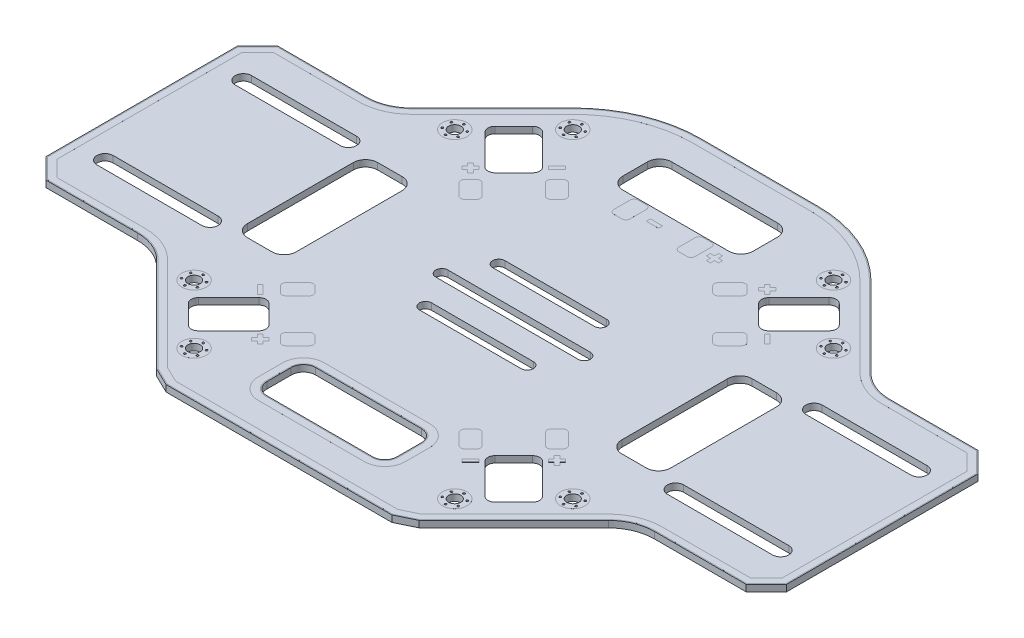
SolidWorks part; units mm, degrees
material "Baseplate Screw Material"
ref_plane "Front Plane" through (0, 0, 0) normal (0, 0, 1) x (1, 0, 0)
ref_plane "Top Plane" through (0, 0, 0) normal (0, 1, 0) x (1, 0, 0)
ref_plane "Right Plane" through (0, 0, 0) normal (1, 0, 0) x (0, 0, -1)
sketch "Sketch1" plane through (0, 0, 0) normal (0, 1, 0) x (1, 0, 0)
  line L0 (0, 60.3186) -> (0, -57.6814) construction
  line L1 (-27.75, -57.6814) -> (27.75, -57.6814)
  line L2 (-13, -47.6814) -> (13, -47.6814)
  line L3 (-16, -38.6814) -> (-16, -44.6814)
  line L4 (16, -38.6814) -> (16, -44.6814)
  line L5 (-16, -41.6814) -> (16, -41.6814) construction
  line L6 (-13, -35.6814) -> (13, -35.6814)
  line L7 (-27.75, -57.6814) -> (-32.25, -55.502)
  line L8 (27.75, -57.6814) -> (32.25, -55.502)
  line L9 (-32.25, -55.502) -> (32.25, -55.502) construction
  line L10 (32.25, -55.502) -> (55.502, -32.25)
  line L11 (-32.25, -55.502) -> (-55.502, -32.25)
  line L12 (-43.876, 43.876) -> (43.876, -43.876) construction
  line L13 (-43.876, -43.876) -> (43.876, 43.876) construction
  line L14 (37.6888, -42.285) -> (42.285, -37.6888)
  line L15 (27.7893, -34.8604) -> (35.2139, -42.285)
  line L16 (34.8604, -27.7893) -> (42.285, -35.2139)
  line L17 (31.5016, -38.5727) -> (38.5727, -31.5016) construction
  line L18 (27.7893, -32.3855) -> (32.3855, -27.7893)
  line L19 (-38.5727, -31.5016) -> (-31.5016, -38.5727) construction
  line L20 (-35.2139, -42.285) -> (-27.7893, -34.8604)
  line L21 (-42.285, -35.2139) -> (-34.8604, -27.7893)
  line L22 (-32.3855, -27.7893) -> (-27.7893, -32.3855)
  line L23 (-42.285, -37.6888) -> (-37.6888, -42.285)
  line L24 (-63.5, -28.9371) -> (63.5, -28.9371) construction
  line L25 (63.5, -28.9371) -> (86, -28.9371)
  line L26 (-63.5, -28.9371) -> (-86, -28.9371)
  line L27 (-91, -23.9371) -> (-91, 23.0629)
  line L28 (91, -23.9371) -> (91, 23.0629)
  line L29 (-86, -28.9371) -> (-86, 28.0629) construction
  line L30 (86, -28.9371) -> (86, 28.0629) construction
  line L31 (-91, -0.4371) -> (-86, -0.4371) construction
  line L32 (86, -0.4371) -> (91, -0.4371) construction
  line L33 (86, -28.9371) -> (91, -23.9371)
  line L34 (-91, -23.9371) -> (-86, -28.9371)
  line L35 (91, 23.0629) -> (86, 28.0629)
  line L36 (-91, 23.0629) -> (-86, 28.0629)
  line L37 (-56.4271, 31.3248) -> (-36.6281, 51.1238)
  line L38 (36.6281, 51.1238) -> (56.4271, 31.3248)
  line L39 (-35.2139, 42.285) -> (-27.7893, 34.8604)
  line L40 (-36.6281, 51.1238) -> (-27.7893, 42.285) construction
  line L41 (-27.7893, 42.285) -> (-31.5016, 38.5727) construction
  line L42 (-42.285, 35.2139) -> (-34.8604, 27.7893)
  line L43 (-31.5016, 38.5727) -> (-38.5727, 31.5016) construction
  line L44 (-42.285, 37.6888) -> (-37.6888, 42.285)
  line L45 (-32.3855, 27.7893) -> (-27.7893, 32.3855)
  line L46 (-86, 28.0629) -> (-64.3021, 28.0629)
  line L47 (86, 28.0629) -> (64.3021, 28.0629)
  line L48 (37.6888, 42.285) -> (42.285, 37.6888)
  line L49 (27.7893, 32.3855) -> (32.3855, 27.7893)
  line L50 (27.7893, 34.8604) -> (35.2139, 42.285)
  line L51 (34.8604, 27.7893) -> (42.285, 35.2139)
  line L52 (31.5016, 38.5727) -> (38.5727, 31.5016) construction
  line L53 (31.5016, 38.5727) -> (27.7893, 42.285) construction
  line L54 (27.7893, 42.285) -> (36.6281, 51.1238) construction
  line L55 (-14.43, 60.3186) -> (14.43, 60.3186)
  line L56 (-13, 51.8186) -> (13, 51.8186)
  line L57 (-13, 39.8186) -> (13, 39.8186)
  line L58 (16, 48.8186) -> (16, 42.8186)
  line L59 (-16, 48.8186) -> (-16, 42.8186)
  line L60 (-12.5, -10.6814) -> (12.5, -10.6814)
  line L61 (-12.5, -7.6814) -> (12.5, -7.6814)
  line L62 (-17.5, -1.6814) -> (17.5, -1.6814)
  line L63 (-17.5, 1.3186) -> (17.5, 1.3186)
  line L64 (-12.5, 7.3186) -> (12.5, 7.3186)
  line L65 (-12.5, 10.3186) -> (12.5, 10.3186)
  line L66 (-52, 12.5629) -> (-52, -13.4371)
  line L67 (-86, -0.4371) -> (-52, -0.4371) construction
  line L68 (-40, 12.5629) -> (-40, -13.4371)
  line L69 (52, 12.5629) -> (52, -13.4371)
  line L70 (-49, 15.5629) -> (-43, 15.5629)
  line L71 (-49, -16.4371) -> (-43, -16.4371)
  line L72 (86, -0.4371) -> (52, -0.4371) construction
  line L73 (40, 12.5629) -> (40, -13.4371)
  line L74 (43, 15.5629) -> (49, 15.5629)
  line L75 (43, -16.4371) -> (49, -16.4371)
  line L76 (-83, 18.5629) -> (-57.2, 18.5629)
  line L77 (-83, 14.5629) -> (-57.2, 14.5629)
  line L78 (-83, -15.4371) -> (-57.2, -15.4371)
  line L79 (-83, -19.4371) -> (-57.2, -19.4371)
  line L80 (57.2, -15.4371) -> (83, -15.4371)
  line L81 (57.2, -19.4371) -> (83, -19.4371)
  line L82 (57.2, 18.5629) -> (83, 18.5629)
  line L83 (57.2, 14.5629) -> (83, 14.5629)
  line L84 (-46.5276, 32.0319) -> (-32.0319, 46.5276) construction
  line L85 (32.0319, -46.5276) -> (46.5276, -32.0319) construction
  arc A0 (-16, -44.6814) -> (-13, -47.6814) centre (-13, -44.6814) ccw
  arc A1 (-13, -35.6814) -> (-16, -38.6814) centre (-13, -38.6814) ccw
  arc A2 (16, -38.6814) -> (13, -35.6814) centre (13, -38.6814) ccw
  arc A3 (13, -47.6814) -> (16, -44.6814) centre (13, -44.6814) ccw
  arc A4 (27.7893, -32.3855) -> (27.7893, -34.8604) centre (29.0267, -33.6229) ccw
  arc A5 (34.8604, -27.7893) -> (32.3855, -27.7893) centre (33.6229, -29.0267) ccw
  arc A6 (35.2139, -42.285) -> (37.6888, -42.285) centre (36.4514, -41.0475) ccw
  arc A7 (42.285, -37.6888) -> (42.285, -35.2139) centre (41.0475, -36.4514) ccw
  arc A8 (-37.6888, -42.285) -> (-35.2139, -42.285) centre (-36.4514, -41.0475) ccw
  arc A9 (-42.285, -35.2139) -> (-42.285, -37.6888) centre (-41.0475, -36.4514) ccw
  arc A10 (-32.3855, -27.7893) -> (-34.8604, -27.7893) centre (-33.6229, -29.0267) ccw
  arc A11 (-27.7893, -34.8604) -> (-27.7893, -32.3855) centre (-29.0267, -33.6229) ccw
  arc A12 (-55.502, -32.25) -> (-63.5, -28.9371) centre (-63.5, -40.248) ccw
  arc A13 (63.5, -28.9371) -> (55.502, -32.25) centre (63.5, -40.248) ccw
  arc A14 (-42.285, 37.6888) -> (-42.285, 35.2139) centre (-41.0475, 36.4514) ccw
  arc A15 (-35.2139, 42.285) -> (-37.6888, 42.285) centre (-36.4514, 41.0475) ccw
  arc A16 (-27.7893, 32.3855) -> (-27.7893, 34.8604) centre (-29.0267, 33.6229) ccw
  arc A17 (-34.8604, 27.7893) -> (-32.3855, 27.7893) centre (-33.6229, 29.0267) ccw
  arc A18 (-64.3021, 28.0629) -> (-56.4271, 31.3248) centre (-64.3021, 39.1998) ccw
  arc A19 (56.4271, 31.3248) -> (64.3021, 28.0629) centre (64.3021, 39.1998) ccw
  arc A20 (27.7893, 34.8604) -> (27.7893, 32.3855) centre (29.0267, 33.6229) ccw
  arc A21 (37.6888, 42.285) -> (35.2139, 42.285) centre (36.4514, 41.0475) ccw
  arc A22 (42.285, 35.2139) -> (42.285, 37.6888) centre (41.0475, 36.4514) ccw
  arc A23 (32.3855, 27.7893) -> (34.8604, 27.7893) centre (33.6229, 29.0267) ccw
  arc A24 (-14.43, 60.3186) -> (-36.6281, 51.1238) centre (-14.43, 28.9257) ccw
  arc A25 (13, 39.8186) -> (16, 42.8186) centre (13, 42.8186) ccw
  arc A26 (36.6281, 51.1238) -> (14.43, 60.3186) centre (14.43, 28.9257) ccw
  arc A27 (16, 48.8186) -> (13, 51.8186) centre (13, 48.8186) ccw
  arc A28 (-16, 42.8186) -> (-13, 39.8186) centre (-13, 42.8186) ccw
  arc A29 (-13, 51.8186) -> (-16, 48.8186) centre (-13, 48.8186) ccw
  arc A30 (-12.5, -7.6814) -> (-12.5, -10.6814) centre (-12.5, -9.1814) ccw
  arc A31 (12.5, -10.6814) -> (12.5, -7.6814) centre (12.5, -9.1814) ccw
  arc A32 (-17.5, 1.3186) -> (-17.5, -1.6814) centre (-17.5, -0.1814) ccw
  arc A33 (17.5, -1.6814) -> (17.5, 1.3186) centre (17.5, -0.1814) ccw
  arc A34 (-12.5, 10.3186) -> (-12.5, 7.3186) centre (-12.5, 8.8186) ccw
  arc A35 (12.5, 7.3186) -> (12.5, 10.3186) centre (12.5, 8.8186) ccw
  arc A36 (-49, 15.5629) -> (-52, 12.5629) centre (-49, 12.5629) ccw
  arc A37 (-40, 12.5629) -> (-43, 15.5629) centre (-43, 12.5629) ccw
  arc A38 (-52, -13.4371) -> (-49, -16.4371) centre (-49, -13.4371) ccw
  arc A39 (-43, -16.4371) -> (-40, -13.4371) centre (-43, -13.4371) ccw
  arc A40 (43, 15.5629) -> (40, 12.5629) centre (43, 12.5629) ccw
  arc A41 (52, 12.5629) -> (49, 15.5629) centre (49, 12.5629) ccw
  arc A42 (40, -13.4371) -> (43, -16.4371) centre (43, -13.4371) ccw
  arc A43 (49, -16.4371) -> (52, -13.4371) centre (49, -13.4371) ccw
  arc A44 (-57.2, 14.5629) -> (-57.2, 18.5629) centre (-57.2, 16.5629) ccw
  arc A45 (-83, 18.5629) -> (-83, 14.5629) centre (-83, 16.5629) ccw
  arc A46 (-83, -15.4371) -> (-83, -19.4371) centre (-83, -17.4371) ccw
  arc A47 (-57.2, -19.4371) -> (-57.2, -15.4371) centre (-57.2, -17.4371) ccw
  arc A48 (57.2, -15.4371) -> (57.2, -19.4371) centre (57.2, -17.4371) ccw
  arc A49 (83, -19.4371) -> (83, -15.4371) centre (83, -17.4371) ccw
  arc A50 (57.2, 18.5629) -> (57.2, 14.5629) centre (57.2, 16.5629) ccw
  arc A51 (83, 14.5629) -> (83, 18.5629) centre (83, 16.5629) ccw
  circle A52 centre (-32.0319, 46.5276) radius 1.5
  circle A53 centre (-46.5276, 32.0319) radius 1.5
  circle A54 centre (32.0319, -46.5276) radius 1.5
  circle A55 centre (46.5276, -32.0319) radius 1.5
  circle A56 centre (-46.5276, -32.0319) radius 1.5
  circle A57 centre (-32.0319, -46.5276) radius 1.5
  circle A58 centre (32.0319, 46.5276) radius 1.5
  circle A59 centre (46.5276, 32.0319) radius 1.5
  point P4 (-35.0371, 35.0371)
  point P5 (0, -47.6814)
  point P14 (0, -41.6814)
  point P15 (0, -35.6814)
  point P19 (0, -55.502)
  point P29 (0, 0)
  point P30 (39.9869, -39.9869)
  point P32 (0, 0)
  point P42 (30.0874, -30.0874)
  point P43 (35.0371, -35.0371)
  point P50 (-35.0371, -35.0371)
  point P53 (-38.5727, -31.5016)
  point P62 (-39.9869, -39.9869)
  point P63 (-30.0874, -30.0874)
  point P70 (0, -28.9371)
  point P99 (-39.9869, 39.9869)
  point P102 (-30.0874, 30.0874)
  point P119 (35.0371, 35.0371)
  point P122 (39.9869, 39.9869)
  point P123 (30.0874, 30.0874)
  point P135 (0, 51.8186)
  point P138 (0, 39.8186)
  point P147 (0, -10.6814)
  point P151 (-14, -9.1814)
  point P153 (14, -9.1814)
  point P156 (0, -1.6814)
  point P158 (-19, -0.1814)
  point P162 (19, -0.1814)
  point P167 (0, 7.3186)
  point P203 (-85, 16.5629)
  point P205 (-55.2, 16.5629)
  point P217 (85, -17.4371)
  point P229 (-39.2798, 39.2798)
  point P232 (39.2798, -39.2798)
  dimension "D5" = 12
  dimension "D6" = 55.5
  dimension "D14" = 14
  dimension "D15" = 127
  dimension "D16" = 22.5
  dimension "D23" = 8.5
  dimension "D24" = 25
  dimension "D25" = 3
  dimension "D28" = 3
  dimension "D31" = 39
  dimension "D32" = 9.5
  dimension "D34" = 29.8
  dimension "D38" = 6
  dimension "D39" = 3
  dimension "D1" = 118
  dimension "D2" = 10
  dimension "D3" = 32
  dimension "D4" = 6
  dimension "D7" = 64.5
  dimension "D8" = 5
  dimension "D9" = 124.1
  dimension "D10" = 45
  dimension "D11" = 5.5
  dimension "D12" = 6.5
  dimension "D13" = 10
  dimension "D17" = 22.5
  dimension "D18" = 5
  dimension "D19" = 45
  dimension "D20" = 47
  dimension "D21" = 28
  dimension "D22" = 5.25
  dimension "D26" = 28
  dimension "D27" = 6
  dimension "D29" = 38
  dimension "D30" = 6
  dimension "D33" = 4
  dimension "D35" = 6
  dimension "D36" = 9.5
  dimension "D37" = 4
  dimension "D40" = 6.5
  dimension "D41" = 6.5
extrude "Boss-Extrude1" add sketch "Sketch1" along normal blind 0.8 and the other way blind 0.8
sketch "Sketch2" plane through (0, 0.8, 0) normal (0, 1, 0) x (1, 0, 0)
  line L0 (-27.6926, -57.4314) -> (27.6926, -57.4314)
  line L1 (-27.75, -57.6814) -> (27.75, -57.6814) construction
  line L2 (-27.6926, -57.4314) -> (-32.1031, -55.2953)
  line L3 (-32.25, -55.502) -> (-27.75, -57.6814) construction
  line L4 (27.6926, -57.4314) -> (32.1031, -55.2953)
  line L5 (27.75, -57.6814) -> (32.25, -55.502) construction
  line L6 (0, -57.6814) -> (0, -57.4314) construction
  line L7 (-32.1031, -55.2953) -> (-55.3252, -32.0732)
  line L8 (-55.502, -32.25) -> (-32.25, -55.502) construction
  line L9 (32.1031, -55.2953) -> (55.3252, -32.0732)
  line L10 (32.25, -55.502) -> (55.502, -32.25) construction
  line L11 (-85.8964, -28.6871) -> (-63.5, -28.6871)
  line L12 (-85.8964, -28.6871) -> (-90.75, -23.8335)
  line L13 (-91, -23.9371) -> (-86, -28.9371) construction
  line L14 (-86, -28.9371) -> (-63.5, -28.9371) construction
  line L15 (63.5, -28.6871) -> (85.8964, -28.6871)
  line L16 (85.8964, -28.6871) -> (90.75, -23.8335)
  line L17 (-90.75, -23.8335) -> (-90.75, 22.9593)
  line L18 (-91, 23.0629) -> (-91, -23.9371) construction
  line L19 (-90.75, 22.9593) -> (-85.8964, 27.8129)
  line L20 (-85.8964, 27.8129) -> (-64.3021, 27.8129)
  line L21 (-64.3021, 28.0629) -> (-86, 28.0629) construction
  line L22 (-56.2503, 31.1481) -> (-36.4514, 50.947)
  line L23 (-36.6281, 51.1238) -> (-56.4271, 31.3248) construction
  line L24 (-14.43, 60.0686) -> (14.43, 60.0686)
  line L25 (14.43, 60.3186) -> (-14.43, 60.3186) construction
  line L26 (56.2503, 31.1481) -> (36.4514, 50.947)
  line L27 (56.4271, 31.3248) -> (36.6281, 51.1238) construction
  line L28 (64.3021, 27.8129) -> (85.8964, 27.8129)
  line L29 (86, 28.0629) -> (64.3021, 28.0629) construction
  line L30 (85.8964, 27.8129) -> (90.75, 22.9593)
  line L31 (91, 23.0629) -> (86, 28.0629) construction
  line L32 (90.75, 22.9593) -> (90.75, -23.8335)
  line L33 (-55.0836, 29.9813) -> (-35.2846, 49.7803)
  line L34 (-14.43, 58.4186) -> (14.43, 58.4186)
  line L35 (55.0836, 29.9813) -> (35.2846, 49.7803)
  line L36 (64.3021, 26.1629) -> (85.213, 26.1629)
  line L37 (85.213, 26.1629) -> (89.1, 22.2759)
  line L38 (89.1, 22.2759) -> (89.1, -23.1501)
  line L39 (85.213, -27.0371) -> (89.1, -23.1501)
  line L40 (63.5, -27.0371) -> (85.213, -27.0371)
  line L41 (31.1332, -53.9317) -> (54.1584, -30.9065)
  line L42 (27.3141, -55.7814) -> (31.1332, -53.9317)
  line L43 (-27.3141, -55.7814) -> (27.3141, -55.7814)
  line L44 (-27.3141, -55.7814) -> (-31.1332, -53.9317)
  line L45 (-31.1332, -53.9317) -> (-54.1584, -30.9065)
  line L46 (-85.213, -27.0371) -> (-63.5, -27.0371)
  line L47 (-85.213, -27.0371) -> (-89.1, -23.1501)
  line L48 (-89.1, -23.1501) -> (-89.1, 22.2759)
  line L49 (-89.1, 22.2759) -> (-85.213, 26.1629)
  line L50 (-85.213, 26.1629) -> (-64.3021, 26.1629)
  line L51 (-13, -35.4314) -> (13, -35.4314)
  line L52 (-16.25, -38.6814) -> (-16.25, -44.6814)
  line L53 (-13, -47.9314) -> (13, -47.9314)
  line L54 (16.25, -44.6814) -> (16.25, -38.6814)
  line L55 (16, -44.6814) -> (16, -38.6814) construction
  line L56 (13, -35.6814) -> (-13, -35.6814) construction
  line L57 (-16, -38.6814) -> (-16, -44.6814) construction
  line L58 (-13, -47.6814) -> (13, -47.6814) construction
  line L59 (-13, -33.6314) -> (13, -33.6314)
  line L60 (18.05, -44.6814) -> (18.05, -38.6814)
  line L61 (-13, -49.7314) -> (13, -49.7314)
  line L62 (-18.05, -38.6814) -> (-18.05, -44.6814)
  line L63 (32.0319, -43.5276) -> (32.0319, -44.2776) construction
  line L64 (-32.0319, -44.2776) -> (-33.9805, -45.4026) construction
  line L65 (-33.9805, -45.4026) -> (-33.9805, -47.6526) construction
  line L66 (-33.9805, -47.6526) -> (-32.0319, -48.7776) construction
  line L67 (-32.0319, -48.7776) -> (-30.0834, -47.6526) construction
  line L68 (-30.0834, -47.6526) -> (-30.0834, -45.4026) construction
  line L69 (-30.0834, -45.4026) -> (-32.0319, -44.2776) construction
  line L70 (-46.5276, -29.7819) -> (-48.4762, -30.9069) construction
  line L71 (-48.4762, -30.9069) -> (-48.4762, -33.1569) construction
  line L72 (-48.4762, -33.1569) -> (-46.5276, -34.2819) construction
  line L73 (-46.5276, -34.2819) -> (-44.5791, -33.1569) construction
  line L74 (-44.5791, -33.1569) -> (-44.5791, -30.9069) construction
  line L75 (-44.5791, -30.9069) -> (-46.5276, -29.7819) construction
  line L76 (-46.5276, 34.2819) -> (-48.4762, 33.1569) construction
  line L77 (-48.4762, 33.1569) -> (-48.4762, 30.9069) construction
  line L78 (-48.4762, 30.9069) -> (-46.5276, 29.7819) construction
  line L79 (-46.5276, 29.7819) -> (-44.5791, 30.9069) construction
  line L80 (-44.5791, 30.9069) -> (-44.5791, 33.1569) construction
  line L81 (-44.5791, 33.1569) -> (-46.5276, 34.2819) construction
  line L82 (-32.0319, 48.7776) -> (-33.9805, 47.6526) construction
  line L83 (-33.9805, 47.6526) -> (-33.9805, 45.4026) construction
  line L84 (-33.9805, 45.4026) -> (-32.0319, 44.2776) construction
  line L85 (-32.0319, 44.2776) -> (-30.0834, 45.4026) construction
  line L86 (-30.0834, 45.4026) -> (-30.0834, 47.6526) construction
  line L87 (-30.0834, 47.6526) -> (-32.0319, 48.7776) construction
  line L88 (32.0319, 48.7776) -> (30.0834, 47.6526) construction
  line L89 (30.0834, 47.6526) -> (30.0834, 45.4026) construction
  line L90 (30.0834, 45.4026) -> (32.0319, 44.2776) construction
  line L91 (32.0319, 44.2776) -> (33.9805, 45.4026) construction
  line L92 (33.9805, 45.4026) -> (33.9805, 47.6526) construction
  line L93 (33.9805, 47.6526) -> (32.0319, 48.7776) construction
  line L94 (46.5276, 34.2819) -> (44.5791, 33.1569) construction
  line L95 (44.5791, 33.1569) -> (44.5791, 30.9069) construction
  line L96 (44.5791, 30.9069) -> (46.5276, 29.7819) construction
  line L97 (46.5276, 29.7819) -> (48.4762, 30.9069) construction
  line L98 (48.4762, 30.9069) -> (48.4762, 33.1569) construction
  line L99 (48.4762, 33.1569) -> (46.5276, 34.2819) construction
  line L100 (46.5276, -29.7819) -> (44.5791, -30.9069) construction
  line L101 (44.5791, -30.9069) -> (44.5791, -33.1569) construction
  line L102 (44.5791, -33.1569) -> (46.5276, -34.2819) construction
  line L103 (46.5276, -34.2819) -> (48.4762, -33.1569) construction
  line L104 (48.4762, -33.1569) -> (48.4762, -30.9069) construction
  line L105 (48.4762, -30.9069) -> (46.5276, -29.7819) construction
  line L106 (32.0319, -44.2776) -> (30.0834, -45.4026) construction
  line L107 (30.0834, -45.4026) -> (30.0834, -47.6526) construction
  line L108 (30.0834, -47.6526) -> (32.0319, -48.7776) construction
  line L109 (32.0319, -48.7776) -> (33.9805, -47.6526) construction
  line L110 (33.9805, -47.6526) -> (33.9805, -45.4026) construction
  line L111 (33.9805, -45.4026) -> (32.0319, -44.2776) construction
  line L112 (32.0319, -44.2776) -> (32.0319, -45.0276) construction
  arc A0 (-55.3252, -32.0732) -> (-63.5, -28.6871) centre (-63.5, -40.248) ccw
  arc A1 (-55.502, -32.25) -> (-63.5, -28.9371) centre (-63.5, -40.248) ccw construction
  arc A2 (63.5, -28.6871) -> (55.3252, -32.0732) centre (63.5, -40.248) ccw
  arc A3 (63.5, -28.9371) -> (55.502, -32.25) centre (63.5, -40.248) ccw construction
  arc A4 (-64.3021, 27.8129) -> (-56.2503, 31.1481) centre (-64.3021, 39.1998) ccw
  arc A5 (-64.3021, 28.0629) -> (-56.4271, 31.3248) centre (-64.3021, 39.1998) ccw construction
  arc A6 (-14.43, 60.0686) -> (-36.4514, 50.947) centre (-14.43, 28.9257) ccw
  arc A7 (-14.43, 60.3186) -> (-36.6281, 51.1238) centre (-14.43, 28.9257) ccw construction
  arc A8 (36.4514, 50.947) -> (14.43, 60.0686) centre (14.43, 28.9257) ccw
  arc A9 (36.6281, 51.1238) -> (14.43, 60.3186) centre (14.43, 28.9257) ccw construction
  arc A10 (56.2503, 31.1481) -> (64.3021, 27.8129) centre (64.3021, 39.1998) ccw
  arc A11 (56.4271, 31.3248) -> (64.3021, 28.0629) centre (64.3021, 39.1998) ccw construction
  arc A12 (-14.43, 58.4186) -> (-35.2846, 49.7803) centre (-14.43, 28.9257) ccw
  arc A13 (35.2846, 49.7803) -> (14.43, 58.4186) centre (14.43, 28.9257) ccw
  arc A14 (55.0836, 29.9813) -> (64.3021, 26.1629) centre (64.3021, 39.1998) ccw
  arc A15 (63.5, -27.0371) -> (54.1584, -30.9065) centre (63.5, -40.248) ccw
  arc A16 (-54.1584, -30.9065) -> (-63.5, -27.0371) centre (-63.5, -40.248) ccw
  arc A17 (-64.3021, 26.1629) -> (-55.0836, 29.9813) centre (-64.3021, 39.1998) ccw
  arc A18 (-13, -35.4314) -> (-16.25, -38.6814) centre (-13, -38.6814) ccw
  arc A19 (16.25, -38.6814) -> (13, -35.4314) centre (13, -38.6814) ccw
  arc A20 (-16.25, -44.6814) -> (-13, -47.9314) centre (-13, -44.6814) ccw
  arc A21 (13, -47.9314) -> (16.25, -44.6814) centre (13, -44.6814) ccw
  arc A22 (-13, -35.6814) -> (-16, -38.6814) centre (-13, -38.6814) ccw construction
  arc A23 (-16, -44.6814) -> (-13, -47.6814) centre (-13, -44.6814) ccw construction
  arc A24 (16, -38.6814) -> (13, -35.6814) centre (13, -38.6814) ccw construction
  arc A25 (13, -47.6814) -> (16, -44.6814) centre (13, -44.6814) ccw construction
  arc A26 (18.05, -38.6814) -> (13, -33.6314) centre (13, -38.6814) ccw
  arc A27 (13, -49.7314) -> (18.05, -44.6814) centre (13, -44.6814) ccw
  arc A28 (-18.05, -44.6814) -> (-13, -49.7314) centre (-13, -44.6814) ccw
  arc A29 (-13, -33.6314) -> (-18.05, -38.6814) centre (-13, -38.6814) ccw
  circle A30 centre (-32.0319, -46.5276) radius 1.5
  circle A31 centre (-46.5276, -32.0319) radius 1.5
  circle A32 centre (-46.5276, 32.0319) radius 1.5
  circle A33 centre (-32.0319, 46.5276) radius 1.5
  circle A34 centre (32.0319, 46.5276) radius 1.5
  circle A35 centre (46.5276, 32.0319) radius 1.5
  circle A36 centre (46.5276, -32.0319) radius 1.5
  circle A37 centre (32.0319, -46.5276) radius 1.5
  circle A38 centre (-32.0319, -46.5276) radius 1.5 construction
  circle A39 centre (-46.5276, -32.0319) radius 1.5 construction
  circle A40 centre (-46.5276, 32.0319) radius 1.5 construction
  circle A41 centre (-32.0319, 46.5276) radius 1.5 construction
  circle A42 centre (32.0319, 46.5276) radius 1.5 construction
  circle A43 centre (46.5276, 32.0319) radius 1.5 construction
  circle A44 centre (46.5276, -32.0319) radius 1.5 construction
  circle A45 centre (32.0319, -46.5276) radius 1.5 construction
  circle A46 centre (-32.0319, -46.5276) radius 3
  circle A47 centre (-46.5276, -32.0319) radius 3
  circle A48 centre (-46.5276, 32.0319) radius 3
  circle A49 centre (-32.0319, 46.5276) radius 3
  circle A50 centre (32.0319, 46.5276) radius 3
  circle A51 centre (46.5276, 32.0319) radius 3
  circle A52 centre (46.5276, -32.0319) radius 3
  circle A53 centre (32.0319, -46.5276) radius 3
  circle A54 centre (-32.0319, -46.5276) radius 1.9486 construction
  circle A55 centre (-46.5276, -32.0319) radius 1.9486 construction
  circle A56 centre (-46.5276, 32.0319) radius 1.9486 construction
  circle A57 centre (-32.0319, 46.5276) radius 1.9486 construction
  circle A58 centre (32.0319, 46.5276) radius 1.9486 construction
  circle A59 centre (46.5276, 32.0319) radius 1.9486 construction
  circle A60 centre (46.5276, -32.0319) radius 1.9486 construction
  circle A61 centre (32.0319, -46.5276) radius 1.9486 construction
  circle A62 centre (32.0319, -44.2776) radius 0.25
  circle A63 centre (33.9805, -45.4026) radius 0.25
  circle A64 centre (33.9805, -47.6526) radius 0.25
  circle A65 centre (32.0319, -48.7776) radius 0.25
  circle A66 centre (30.0834, -47.6526) radius 0.25
  circle A67 centre (30.0834, -45.4026) radius 0.25
  circle A68 centre (46.5276, -34.2819) radius 0.25
  circle A69 centre (48.4762, -33.1569) radius 0.25
  circle A70 centre (48.4762, -30.9069) radius 0.25
  circle A71 centre (46.5276, -29.7819) radius 0.25
  circle A72 centre (44.5791, -30.9069) radius 0.25
  circle A73 centre (44.5791, -33.1569) radius 0.25
  circle A74 centre (46.5276, 29.7819) radius 0.25
  circle A75 centre (48.4762, 30.9069) radius 0.25
  circle A76 centre (48.4762, 33.1569) radius 0.25
  circle A77 centre (46.5276, 34.2819) radius 0.25
  circle A78 centre (44.5791, 33.1569) radius 0.25
  circle A79 centre (44.5791, 30.9069) radius 0.25
  circle A80 centre (32.0319, 44.2776) radius 0.25
  circle A81 centre (33.9805, 45.4026) radius 0.25
  circle A82 centre (33.9805, 47.6526) radius 0.25
  circle A83 centre (32.0319, 48.7776) radius 0.25
  circle A84 centre (30.0834, 47.6526) radius 0.25
  circle A85 centre (30.0834, 45.4026) radius 0.25
  circle A86 centre (-32.0319, 48.7776) radius 0.25
  circle A87 centre (-30.0834, 47.6526) radius 0.25
  circle A88 centre (-30.0834, 45.4026) radius 0.25
  circle A89 centre (-32.0319, 44.2776) radius 0.25
  circle A90 centre (-33.9805, 47.6526) radius 0.25
  circle A91 centre (-33.9805, 45.4026) radius 0.25
  circle A92 centre (-46.5276, 29.7819) radius 0.25
  circle A93 centre (-44.5791, 30.9069) radius 0.25
  circle A94 centre (-44.5791, 33.1569) radius 0.25
  circle A95 centre (-46.5276, 34.2819) radius 0.25
  circle A96 centre (-48.4762, 33.1569) radius 0.25
  circle A97 centre (-48.4762, 30.9069) radius 0.25
  circle A98 centre (-46.5276, -29.7819) radius 0.25
  circle A99 centre (-44.5791, -30.9069) radius 0.25
  circle A100 centre (-44.5791, -33.1569) radius 0.25
  circle A101 centre (-46.5276, -34.2819) radius 0.25
  circle A102 centre (-48.4762, -33.1569) radius 0.25
  circle A103 centre (-48.4762, -30.9069) radius 0.25
  circle A104 centre (-32.0319, -44.2776) radius 0.25
  circle A105 centre (-30.0834, -45.4026) radius 0.25
  circle A106 centre (-30.0834, -47.6526) radius 0.25
  circle A107 centre (-32.0319, -48.7776) radius 0.25
  circle A108 centre (-33.9805, -47.6526) radius 0.25
  circle A109 centre (-33.9805, -45.4026) radius 0.25
  dimension "D2" = 0.25
  dimension "D5" = 0.25
  dimension "D7" = 1.65
  dimension "D8" = 0.25
  dimension "D10" = 6
  dimension "D11" = 0.5
  dimension "D1" = 0.25
  dimension "D3" = 0.25
  dimension "D4" = 0.25
  dimension "D6" = 0.25
  dimension "D9" = 1.8
extrude "Boss-Extrude2" add sketch "Sketch2" along normal blind 0.001 contours A10 L26 A8 L24 A6 L22 A4 L20 L19 L17 L12 L11 A0 L7 L2 L0 L4 L9 A2 L15 L16 L32 L30 L28 L50 A17 L33 A12 L34 A13 L35 A14 L36 L37 L38 L39 L40 A15 L41 L42 L43 L44 L45 A16 L46 L47 L48 L49 | A46 A109 A108 A107 A106 A105 A104 A30 | A47 A103 A102 A101 A100 A99 A98 A31 | A48 A97 A96 A95 A94 A93 A92 A32 | A49 A91 A90 A89 A88 A87 A86 A33 | A50 A85 A84 A83 A82 A81 A80 A34 | A51 A79 A78 A77 A76 A75 A74 A35 | A52 A73 A72 A71 A70 A69 A68 A36 | A53 A67 A66 A65 A64 A63 A62 A37 | L59 A29 L62 A28 L61 A27 L60 A26 A21 L53 A20 L52 A18 L51 A19 L54 region at (-29.8036, 0.8, 56.1688) region at (0, 0.8, 34.0267) region at (-34.9471, 0.8, 46.5276) region at (-49.4428, 0.8, 32.0319) region at (-49.4428, 0.8, -32.0319) region at (-34.9471, 0.8, -46.5276) region at (29.1168, 0.8, -46.5276) region at (43.6125, 0.8, -32.0319) region at (43.6125, 0.8, 32.0319) region at (29.1168, 0.8, 46.5276)
mirror "Mirror1" about plane through (0, 0, 0) normal (0, 1, 0) of "Boss-Extrude2"
sketch "Sketch3" plane through (0, -0.8, 0) normal (0, -1, 0) x (1, 0, 0)
  line L0 (0, 49.7314) -> (0, 51.7314) construction
  line L1 (-13, 49.7314) -> (13, 49.7314) construction
  line L2 (-27.3141, 55.7814) -> (27.3141, 55.7814) construction
  line L3 (11, 51.7314) -> (-11, 51.7314) construction
  line L4 (11, 53.7814) -> (-11, 53.7814) construction
  line L5 (0, 53.7814) -> (0, 55.7814) construction
  line L6 (11, 51.7314) -> (11, 53.7814) construction
  line L7 (-11, 51.7314) -> (-11, 53.7814) construction
  line L8 (11.29, 53.7814) -> (-10.71, 53.7814) construction
  text T0 "<b>DJI INNOVATIONS</b>" font "MS Reference Sans Serif" height 2.05
  point P8 (0, 51.7314)
  point P11 (0, 53.7814)
  dimension "D1" = 2
  dimension "D2" = 22
  dimension "D3" = 0.29
extrude "Boss-Extrude3" add sketch "Sketch3" along normal blind 0.001
sketch "Sketch4" plane through (0, -0.8, 0) normal (0, -1, 0) x (1, 0, 0)
  line L0 (9.1282, 51.7314) -> (9.1282, 51.9909)
  line L1 (9.1282, 51.9909) -> (8.7389, 51.9909)
  line L2 (8.7389, 51.9909) -> (8.7389, 51.7314)
  line L3 (9.1282, 51.7314) -> (8.4275, 51.7314) construction
  line L4 (8.7389, 51.7314) -> (9.1282, 51.7314)
  line L6 (-3.2442, 51.7314) -> (-3.2442, 52.0168)
  line L7 (-3.2442, 52.0168) -> (-3.3442, 52.0168)
  line L8 (-3.893, 52.0168) -> (-3.2442, 52.0168) construction
  line L9 (-3.3442, 52.0168) -> (-3.3442, 51.7314)
  line L10 (-3.2442, 51.7314) -> (-4.8531, 51.7314) construction
  line L11 (-3.3442, 51.7314) -> (-3.2442, 51.7314)
  line L12 (-4.8531, 51.7314) -> (-4.7531, 51.7314)
  line L13 (-4.7531, 51.7314) -> (-4.7531, 52.0168)
  line L14 (-4.8531, 52.0168) -> (-4.2044, 52.0168) construction
  line L15 (-4.7531, 52.0168) -> (-4.8531, 52.0168)
  line L16 (-4.8531, 52.0168) -> (-4.8531, 51.7314)
  dimension "D1" = 0.1
extrude "Cut-Extrude1" cut sketch "Sketch4" along normal up to surface (0.001 mm away) up to face at (8.9409, -0.801, 52.931)
sketch "Sketch5" plane through (0, 0.8, 0) normal (0, 1, 0) x (1, 0, 0)
  line L0 (35.7442, -27.259) -> (36.4514, -26.5519)
  line L1 (35.0371, -26.5519) -> (35.7442, -25.8448)
  line L2 (35.3907, -26.9054) -> (37.512, -24.7841) construction
  line L3 (35.0371, -26.5519) -> (35.7442, -27.259)
  line L4 (37.1585, -24.4305) -> (37.8656, -25.1376)
  line L5 (42.285, -35.2139) -> (34.8604, -27.7893) construction
  line L6 (32.1031, -55.2953) -> (55.3252, -32.0732) construction
  line L8 (35.3907, -24.7841) -> (37.512, -26.9054) construction
  line L9 (35.0371, -25.1376) -> (35.7442, -24.4305)
  line L10 (37.1585, -27.259) -> (37.8656, -26.5519)
  line L11 (35.0371, -25.1376) -> (35.7442, -25.8448)
  line L12 (35.7442, -24.4305) -> (36.4514, -25.1376)
  line L13 (36.4514, -26.5519) -> (37.1585, -27.259)
  line L14 (36.4514, -25.1376) -> (37.1585, -24.4305)
  line L15 (37.1585, -25.8448) -> (37.8656, -26.5519)
  line L16 (37.1585, -25.8448) -> (37.8656, -25.1376)
  line L17 (26.9054, -35.3907) -> (24.7841, -37.512) construction
  line L18 (26.5519, -35.0371) -> (27.259, -35.7442)
  line L19 (27.7893, -34.8604) -> (35.2139, -42.285) construction
  line L20 (24.4305, -37.1585) -> (25.1376, -37.8656)
  line L21 (24.4305, -37.1585) -> (26.5519, -35.0371)
  line L22 (25.1376, -37.8656) -> (27.259, -35.7442)
  line L23 (-37.1585, -24.4305) -> (-37.8656, -25.1376)
  line L24 (-37.1585, -24.4305) -> (-35.0371, -26.5519)
  line L25 (-37.8656, -25.1376) -> (-35.7442, -27.259)
  line L26 (-35.3907, -26.9054) -> (-37.512, -24.7841) construction
  line L27 (-35.0371, -26.5519) -> (-35.7442, -27.259)
  line L28 (-26.5519, -35.0371) -> (-27.259, -35.7442)
  line L29 (-27.259, -35.7442) -> (-26.5519, -36.4514)
  line L30 (-26.5519, -36.4514) -> (-27.259, -37.1585)
  line L31 (-27.259, -37.1585) -> (-26.5519, -37.8656)
  line L32 (-25.8448, -37.1585) -> (-26.5519, -37.8656)
  line L33 (-25.8448, -37.1585) -> (-25.1376, -37.8656)
  line L34 (-24.4305, -37.1585) -> (-25.1376, -37.8656)
  line L35 (-25.1376, -36.4514) -> (-24.4305, -37.1585)
  line L36 (-24.4305, -35.7442) -> (-25.1376, -36.4514)
  line L37 (-25.1376, -35.0371) -> (-24.4305, -35.7442)
  line L38 (-25.1376, -35.0371) -> (-25.8448, -35.7442)
  line L39 (-26.5519, -35.0371) -> (-25.8448, -35.7442)
  line L40 (-26.9054, -35.3907) -> (-24.7841, -37.512) construction
  line L41 (-24.7841, -35.3907) -> (-26.9054, -37.512) construction
  line L42 (-24.4305, 37.1585) -> (-25.1376, 37.8656)
  line L43 (-24.4305, 37.1585) -> (-26.5519, 35.0371)
  line L44 (-25.1376, 37.8656) -> (-27.259, 35.7442)
  line L45 (-26.9054, 35.3907) -> (-24.7841, 37.512) construction
  line L46 (-26.5519, 35.0371) -> (-27.259, 35.7442)
  line L47 (-35.0371, 26.5519) -> (-35.7442, 27.259)
  line L48 (-35.7442, 27.259) -> (-36.4514, 26.5519)
  line L49 (-36.4514, 26.5519) -> (-37.1585, 27.259)
  line L50 (-37.1585, 27.259) -> (-37.8656, 26.5519)
  line L51 (-37.1585, 25.8448) -> (-37.8656, 26.5519)
  line L52 (-37.1585, 25.8448) -> (-37.8656, 25.1376)
  line L53 (-37.1585, 24.4305) -> (-37.8656, 25.1376)
  line L54 (-36.4514, 25.1376) -> (-37.1585, 24.4305)
  line L55 (-35.7442, 24.4305) -> (-36.4514, 25.1376)
  line L56 (-35.0371, 25.1376) -> (-35.7442, 24.4305)
  line L57 (-35.0371, 25.1376) -> (-35.7442, 25.8448)
  line L58 (-35.0371, 26.5519) -> (-35.7442, 25.8448)
  line L59 (-35.3907, 26.9054) -> (-37.512, 24.7841) construction
  line L60 (-35.3907, 24.7841) -> (-37.512, 26.9054) construction
  line L61 (37.1585, 24.4305) -> (37.8656, 25.1376)
  line L62 (37.1585, 24.4305) -> (35.0371, 26.5519)
  line L63 (37.8656, 25.1376) -> (35.7442, 27.259)
  line L64 (35.3907, 26.9054) -> (37.512, 24.7841) construction
  line L65 (35.0371, 26.5519) -> (35.7442, 27.259)
  line L66 (26.5519, 35.0371) -> (27.259, 35.7442)
  line L67 (27.259, 35.7442) -> (26.5519, 36.4514)
  line L68 (26.5519, 36.4514) -> (27.259, 37.1585)
  line L69 (27.259, 37.1585) -> (26.5519, 37.8656)
  line L70 (25.8448, 37.1585) -> (26.5519, 37.8656)
  line L71 (25.8448, 37.1585) -> (25.1376, 37.8656)
  line L72 (24.4305, 37.1585) -> (25.1376, 37.8656)
  line L73 (25.1376, 36.4514) -> (24.4305, 37.1585)
  line L74 (24.4305, 35.7442) -> (25.1376, 36.4514)
  line L75 (25.1376, 35.0371) -> (24.4305, 35.7442)
  line L76 (25.1376, 35.0371) -> (25.8448, 35.7442)
  line L77 (26.5519, 35.0371) -> (25.8448, 35.7442)
  line L78 (26.9054, 35.3907) -> (24.7841, 37.512) construction
  line L79 (24.7841, 35.3907) -> (26.9054, 37.512) construction
  line L80 (-36.6281, 51.1238) -> (-56.4271, 31.3248) construction
  line L81 (29.0267, -19.8343) -> (30.4409, -18.4201)
  line L82 (31.8552, -18.4201) -> (34.6836, -21.2486)
  line L83 (29.0267, -21.2486) -> (31.8552, -24.077)
  line L84 (33.2694, -24.077) -> (34.6836, -22.6628)
  line L85 (30.4409, -22.6628) -> (33.2694, -19.8343) construction
  line L86 (29.7338, -19.1272) -> (33.9765, -23.3699) construction
  line L87 (32.3855, -27.7893) -> (27.7893, -32.3855) construction
  line L88 (18.4201, -31.8552) -> (21.2486, -34.6836)
  line L89 (18.4201, -30.4409) -> (19.8343, -29.0267)
  line L90 (21.2486, -29.0267) -> (24.077, -31.8552)
  line L91 (22.6628, -34.6836) -> (24.077, -33.2694)
  line L92 (19.8343, -33.2694) -> (22.6628, -30.4409) construction
  line L93 (19.1272, -29.7338) -> (23.3699, -33.9765) construction
  line L94 (-34.6836, -22.6628) -> (-33.2694, -24.077)
  line L95 (-31.8552, -18.4201) -> (-34.6836, -21.2486)
  line L96 (-30.4409, -18.4201) -> (-29.0267, -19.8343)
  line L97 (-29.0267, -21.2486) -> (-31.8552, -24.077)
  line L98 (-29.7338, -19.1272) -> (-33.9765, -23.3699) construction
  line L99 (-33.2694, -19.8343) -> (-30.4409, -22.6628) construction
  line L100 (-21.2486, -29.0267) -> (-24.077, -31.8552)
  line L101 (-24.077, -33.2694) -> (-22.6628, -34.6836)
  line L102 (-18.4201, -31.8552) -> (-21.2486, -34.6836)
  line L103 (-19.8343, -29.0267) -> (-18.4201, -30.4409)
  line L104 (-19.1272, -29.7338) -> (-23.3699, -33.9765) construction
  line L105 (-22.6628, -30.4409) -> (-19.8343, -33.2694) construction
  line L106 (-22.6628, 34.6836) -> (-24.077, 33.2694)
  line L107 (-18.4201, 31.8552) -> (-21.2486, 34.6836)
  line L108 (-18.4201, 30.4409) -> (-19.8343, 29.0267)
  line L109 (-21.2486, 29.0267) -> (-24.077, 31.8552)
  line L110 (-19.1272, 29.7338) -> (-23.3699, 33.9765) construction
  line L111 (-19.8343, 33.2694) -> (-22.6628, 30.4409) construction
  line L112 (-29.0267, 21.2486) -> (-31.8552, 24.077)
  line L113 (-33.2694, 24.077) -> (-34.6836, 22.6628)
  line L114 (-31.8552, 18.4201) -> (-34.6836, 21.2486)
  line L115 (-29.0267, 19.8343) -> (-30.4409, 18.4201)
  line L116 (-29.7338, 19.1272) -> (-33.9765, 23.3699) construction
  line L117 (-30.4409, 22.6628) -> (-33.2694, 19.8343) construction
  line L118 (34.6836, 22.6628) -> (33.2694, 24.077)
  line L119 (31.8552, 18.4201) -> (34.6836, 21.2486)
  line L120 (30.4409, 18.4201) -> (29.0267, 19.8343)
  line L121 (29.0267, 21.2486) -> (31.8552, 24.077)
  line L122 (29.7338, 19.1272) -> (33.9765, 23.3699) construction
  line L123 (33.2694, 19.8343) -> (30.4409, 22.6628) construction
  line L124 (21.2486, 29.0267) -> (24.077, 31.8552)
  line L125 (24.077, 33.2694) -> (22.6628, 34.6836)
  line L126 (18.4201, 31.8552) -> (21.2486, 34.6836)
  line L127 (19.8343, 29.0267) -> (18.4201, 30.4409)
  line L128 (19.1272, 29.7338) -> (23.3699, 33.9765) construction
  line L129 (22.6628, 30.4409) -> (19.8343, 33.2694) construction
  line L130 (32.25, -55.502) -> (55.502, -32.25) construction
  arc A0 (31.8552, -18.4201) -> (30.4409, -18.4201) centre (31.1481, -19.1272) ccw
  arc A1 (29.0267, -19.8343) -> (29.0267, -21.2486) centre (29.7338, -20.5415) ccw
  arc A2 (31.8552, -24.077) -> (33.2694, -24.077) centre (32.5623, -23.3699) ccw
  arc A3 (34.6836, -22.6628) -> (34.6836, -21.2486) centre (33.9765, -21.9557) ccw
  arc A4 (18.4201, -30.4409) -> (18.4201, -31.8552) centre (19.1272, -31.1481) ccw
  arc A5 (21.2486, -29.0267) -> (19.8343, -29.0267) centre (20.5415, -29.7338) ccw
  arc A6 (24.077, -33.2694) -> (24.077, -31.8552) centre (23.3699, -32.5623) ccw
  arc A7 (21.2486, -34.6836) -> (22.6628, -34.6836) centre (21.9557, -33.9765) ccw
  arc A8 (-33.2694, -24.077) -> (-31.8552, -24.077) centre (-32.5623, -23.3699) ccw
  arc A9 (-34.6836, -21.2486) -> (-34.6836, -22.6628) centre (-33.9765, -21.9557) ccw
  arc A10 (-30.4409, -18.4201) -> (-31.8552, -18.4201) centre (-31.1481, -19.1272) ccw
  arc A11 (-29.0267, -21.2486) -> (-29.0267, -19.8343) centre (-29.7338, -20.5415) ccw
  arc A12 (-24.077, -31.8552) -> (-24.077, -33.2694) centre (-23.3699, -32.5623) ccw
  arc A13 (-22.6628, -34.6836) -> (-21.2486, -34.6836) centre (-21.9557, -33.9765) ccw
  arc A14 (-18.4201, -31.8552) -> (-18.4201, -30.4409) centre (-19.1272, -31.1481) ccw
  arc A15 (-19.8343, -29.0267) -> (-21.2486, -29.0267) centre (-20.5415, -29.7338) ccw
  arc A16 (-24.077, 33.2694) -> (-24.077, 31.8552) centre (-23.3699, 32.5623) ccw
  arc A17 (-21.2486, 34.6836) -> (-22.6628, 34.6836) centre (-21.9557, 33.9765) ccw
  arc A18 (-18.4201, 30.4409) -> (-18.4201, 31.8552) centre (-19.1272, 31.1481) ccw
  arc A19 (-21.2486, 29.0267) -> (-19.8343, 29.0267) centre (-20.5415, 29.7338) ccw
  arc A20 (-31.8552, 24.077) -> (-33.2694, 24.077) centre (-32.5623, 23.3699) ccw
  arc A21 (-34.6836, 22.6628) -> (-34.6836, 21.2486) centre (-33.9765, 21.9557) ccw
  arc A22 (-31.8552, 18.4201) -> (-30.4409, 18.4201) centre (-31.1481, 19.1272) ccw
  arc A23 (-29.0267, 19.8343) -> (-29.0267, 21.2486) centre (-29.7338, 20.5415) ccw
  arc A24 (33.2694, 24.077) -> (31.8552, 24.077) centre (32.5623, 23.3699) ccw
  arc A25 (34.6836, 21.2486) -> (34.6836, 22.6628) centre (33.9765, 21.9557) ccw
  arc A26 (30.4409, 18.4201) -> (31.8552, 18.4201) centre (31.1481, 19.1272) ccw
  arc A27 (29.0267, 21.2486) -> (29.0267, 19.8343) centre (29.7338, 20.5415) ccw
  arc A28 (24.077, 31.8552) -> (24.077, 33.2694) centre (23.3699, 32.5623) ccw
  arc A29 (22.6628, 34.6836) -> (21.2486, 34.6836) centre (21.9557, 33.9765) ccw
  arc A30 (18.4201, 31.8552) -> (18.4201, 30.4409) centre (19.1272, 31.1481) ccw
  arc A31 (19.8343, 29.0267) -> (21.2486, 29.0267) centre (20.5415, 29.7338) ccw
  point P14 (36.4514, -25.8448)
  point P17 (35.3907, -24.7841)
  point P101 (0, 0)
  point P111 (31.8552, -21.2486)
  point P234 (0, 0)
  dimension "D8" = 2
  dimension "D1" = 3
  dimension "D2" = 1
  dimension "D3" = 18
  dimension "D4" = 1
  dimension "D5" = 1
  dimension "D6" = 4
  dimension "D7" = 18
  dimension "D9" = 4
  dimension "D10" = 2
  dimension "D11" = 4
  dimension "D13" = 4
  dimension "D12" = 15
  dimension "D14" = 2
extrude "Boss-Extrude4" add sketch "Sketch5" along normal blind 0.001
sketch "Sketch6" plane through (0, 0.8, 0) normal (0, 1, 0) x (1, 0, 0)
  circle A0 centre (-48.4762, 33.1569) radius 0.25
  circle A1 centre (-46.5276, 34.2819) radius 0.25
  circle A2 centre (-44.5791, 33.1569) radius 0.25
  circle A3 centre (-48.4762, 30.9069) radius 0.25
  circle A4 centre (-46.5276, 29.7819) radius 0.25
  circle A5 centre (-44.5791, 30.9069) radius 0.25
  circle A6 centre (-33.9805, 45.4026) radius 0.25
  circle A7 centre (-32.0319, 48.7776) radius 0.25
  circle A8 centre (-33.9805, 47.6526) radius 0.25
  circle A9 centre (-32.0319, 44.2776) radius 0.25
  circle A10 centre (-30.0834, 47.6526) radius 0.25
  circle A11 centre (-30.0834, 45.4026) radius 0.25
  circle A12 centre (30.0834, 47.6526) radius 0.25
  circle A13 centre (32.0319, 48.7776) radius 0.25
  circle A14 centre (33.9805, 47.6526) radius 0.25
  circle A15 centre (33.9805, 45.4026) radius 0.25
  circle A16 centre (30.0834, 45.4026) radius 0.25
  circle A17 centre (32.0319, 44.2776) radius 0.25
  circle A18 centre (46.5276, 34.2819) radius 0.25
  circle A19 centre (48.4762, 30.9069) radius 0.25
  circle A20 centre (44.5791, 33.1569) radius 0.25
  circle A21 centre (48.4762, 33.1569) radius 0.25
  circle A22 centre (46.5276, 29.7819) radius 0.25
  circle A23 centre (44.5791, 30.9069) radius 0.25
  circle A24 centre (44.5791, -30.9069) radius 0.25
  circle A25 centre (46.5276, -29.7819) radius 0.25
  circle A26 centre (44.5791, -33.1569) radius 0.25
  circle A27 centre (48.4762, -33.1569) radius 0.25
  circle A28 centre (48.4762, -30.9069) radius 0.25
  circle A29 centre (46.5276, -34.2819) radius 0.25
  circle A30 centre (32.0319, -44.2776) radius 0.25
  circle A31 centre (30.0834, -45.4026) radius 0.25
  circle A32 centre (30.0834, -47.6526) radius 0.25
  circle A33 centre (33.9805, -47.6526) radius 0.25
  circle A34 centre (32.0319, -48.7776) radius 0.25
  circle A35 centre (33.9805, -45.4026) radius 0.25
  circle A36 centre (-48.4762, -30.9069) radius 0.25
  circle A37 centre (-44.5791, -30.9069) radius 0.25
  circle A38 centre (-48.4762, -33.1569) radius 0.25
  circle A39 centre (-46.5276, -34.2819) radius 0.25
  circle A40 centre (-44.5791, -33.1569) radius 0.25
  circle A41 centre (-46.5276, -29.7819) radius 0.25
  circle A42 centre (-33.9805, -45.4026) radius 0.25
  circle A43 centre (-32.0319, -44.2776) radius 0.25
  circle A44 centre (-30.0834, -45.4026) radius 0.25
  circle A45 centre (-30.0834, -47.6526) radius 0.25
  circle A46 centre (-33.9805, -47.6526) radius 0.25
  circle A47 centre (-32.0319, -48.7776) radius 0.25
  circle A48 centre (-48.4762, 33.1569) radius 0.25 construction
  circle A49 centre (-46.5276, 34.2819) radius 0.25 construction
  circle A50 centre (-44.5791, 33.1569) radius 0.25 construction
  circle A51 centre (-44.5791, 30.9069) radius 0.25 construction
  circle A52 centre (-46.5276, 29.7819) radius 0.25 construction
  circle A53 centre (-48.4762, 30.9069) radius 0.25 construction
  circle A54 centre (-33.9805, 45.4026) radius 0.25 construction
  circle A55 centre (-33.9805, 47.6526) radius 0.25 construction
  circle A56 centre (-32.0319, 48.7776) radius 0.25 construction
  circle A57 centre (-30.0834, 47.6526) radius 0.25 construction
  circle A58 centre (-30.0834, 45.4026) radius 0.25 construction
  circle A59 centre (-32.0319, 44.2776) radius 0.25 construction
  circle A60 centre (32.0319, 44.2776) radius 0.25 construction
  circle A61 centre (30.0834, 45.4026) radius 0.25 construction
  circle A62 centre (30.0834, 47.6526) radius 0.25 construction
  circle A63 centre (32.0319, 48.7776) radius 0.25 construction
  circle A64 centre (33.9805, 47.6526) radius 0.25 construction
  circle A65 centre (33.9805, 45.4026) radius 0.25 construction
  circle A66 centre (46.5276, 34.2819) radius 0.25 construction
  circle A67 centre (44.5791, 33.1569) radius 0.25 construction
  circle A68 centre (44.5791, 30.9069) radius 0.25 construction
  circle A69 centre (48.4762, 33.1569) radius 0.25 construction
  circle A70 centre (46.5276, 29.7819) radius 0.25 construction
  circle A71 centre (48.4762, 30.9069) radius 0.25 construction
  circle A72 centre (44.5791, -30.9069) radius 0.25 construction
  circle A73 centre (46.5276, -29.7819) radius 0.25 construction
  circle A74 centre (48.4762, -30.9069) radius 0.25 construction
  circle A75 centre (48.4762, -33.1569) radius 0.25 construction
  circle A76 centre (44.5791, -33.1569) radius 0.25 construction
  circle A77 centre (46.5276, -34.2819) radius 0.25 construction
  circle A78 centre (32.0319, -44.2776) radius 0.25 construction
  circle A79 centre (30.0834, -45.4026) radius 0.25 construction
  circle A80 centre (33.9805, -45.4026) radius 0.25 construction
  circle A81 centre (30.0834, -47.6526) radius 0.25 construction
  circle A82 centre (33.9805, -47.6526) radius 0.25 construction
  circle A83 centre (32.0319, -48.7776) radius 0.25 construction
  circle A84 centre (-32.0319, -48.7776) radius 0.25 construction
  circle A85 centre (-33.9805, -47.6526) radius 0.25 construction
  circle A86 centre (-33.9805, -45.4026) radius 0.25 construction
  circle A87 centre (-32.0319, -44.2776) radius 0.25 construction
  circle A88 centre (-30.0834, -45.4026) radius 0.25 construction
  circle A89 centre (-30.0834, -47.6526) radius 0.25 construction
  circle A90 centre (-46.5276, -34.2819) radius 0.25 construction
  circle A91 centre (-48.4762, -33.1569) radius 0.25 construction
  circle A92 centre (-48.4762, -30.9069) radius 0.25 construction
  circle A93 centre (-46.5276, -29.7819) radius 0.25 construction
  circle A94 centre (-44.5791, -30.9069) radius 0.25 construction
  circle A95 centre (-44.5791, -33.1569) radius 0.25 construction
extrude "Cut-Extrude2" cut sketch "Sketch6" against normal up to surface (1.6 mm away) up to face at (-4.0487, -0.8, 52.3866)
sketch "Sketch7" plane through (0, 0.8, 0) normal (0, 1, 0) x (1, 0, 0)
  line L0 (9, 39.5686) -> (7, 39.5686)
  line L1 (-7, 39.5686) -> (-9, 39.5686)
  line L2 (8, 39.5686) -> (-8, 39.5686) construction
  line L3 (0, 39.5686) -> (0, 39.8186) construction
  line L4 (-13, 39.8186) -> (13, 39.8186) construction
  line L5 (10, 38.5686) -> (10, 34.5686)
  line L6 (6, 34.5686) -> (6, 38.5686)
  line L7 (9, 33.5686) -> (7, 33.5686)
  line L8 (8, 39.5686) -> (8, 33.5686) construction
  line L9 (10, 36.5686) -> (6, 36.5686) construction
  line L10 (-6, 38.5686) -> (-6, 34.5686)
  line L11 (-7, 33.5686) -> (-9, 33.5686)
  line L12 (-10, 34.5686) -> (-10, 38.5686)
  line L13 (-8, 39.5686) -> (-8, 33.5686) construction
  line L14 (-6, 36.5686) -> (-10, 36.5686) construction
  line L15 (-3.5, 36.0686) -> (-3.5, 37.0686)
  line L16 (-3.5, 37.0686) -> (-0.5, 37.0686)
  line L17 (-0.5, 37.0686) -> (-0.5, 36.0686)
  line L18 (-0.5, 36.0686) -> (-3.5, 36.0686)
  line L19 (-0.5, 36.5686) -> (-3.5, 36.5686) construction
  line L20 (14.25, 36.0686) -> (13.25, 36.0686)
  line L21 (11.25, 36.0686) -> (11.25, 37.0686)
  line L22 (11.25, 37.0686) -> (12.25, 37.0686)
  line L23 (14.25, 37.0686) -> (14.25, 36.0686)
  line L24 (14.25, 36.5686) -> (11.25, 36.5686) construction
  line L25 (12.75, 38.0686) -> (12.75, 35.0686) construction
  line L26 (13.25, 35.0686) -> (12.25, 35.0686)
  line L27 (13.25, 38.0686) -> (12.25, 38.0686)
  line L28 (13.25, 35.0686) -> (13.25, 36.0686)
  line L29 (12.25, 35.0686) -> (12.25, 36.0686)
  line L30 (13.25, 37.0686) -> (13.25, 38.0686)
  line L31 (12.25, 36.0686) -> (11.25, 36.0686)
  line L32 (13.25, 37.0686) -> (14.25, 37.0686)
  line L33 (12.25, 37.0686) -> (12.25, 38.0686)
  arc A0 (10, 38.5686) -> (9, 39.5686) centre (9, 38.5686) ccw
  arc A1 (7, 39.5686) -> (6, 38.5686) centre (7, 38.5686) ccw
  arc A3 (9, 33.5686) -> (10, 34.5686) centre (9, 34.5686) ccw
  arc A4 (6, 34.5686) -> (7, 33.5686) centre (7, 34.5686) ccw
  arc A5 (-6, 38.5686) -> (-7, 39.5686) centre (-7, 38.5686) ccw
  arc A6 (-9, 39.5686) -> (-10, 38.5686) centre (-9, 38.5686) ccw
  arc A7 (-7, 33.5686) -> (-6, 34.5686) centre (-7, 34.5686) ccw
  arc A8 (-10, 34.5686) -> (-9, 33.5686) centre (-9, 34.5686) ccw
  point P50 (12.75, 36.5686)
  point P55 (12.75, 35.0686)
  point P56 (12.75, 38.0686)
  dimension "D4" = 4
  dimension "D6" = 2.5
  dimension "D1" = 2
  dimension "D2" = 16
  dimension "D3" = 0.25
  dimension "D5" = 4
  dimension "D7" = 3
  dimension "D8" = 1
  dimension "D9" = 3
  dimension "D10" = 1.25
extrude "Boss-Extrude5" add sketch "Sketch7" along normal blind 0.001
sketch3d "3DSketch1"
  line L0 (-32.0319, 0.801, -46.5276) -> (-32.0319, -0.801, -46.5276) construction
  line L1 (-32.0319, -0.801, -46.5276) -> (-32.0319, 0.801, -46.5276) construction
  line L2 (-32.0319, -0.801, -46.5276) -> (-32.0319, -0.8, -46.5276) construction
  line L3 (-46.5276, 0.801, -32.0319) -> (-46.5276, -0.801, -32.0319) construction
  line L4 (-46.5276, -0.801, -32.0319) -> (-46.5276, 0.801, -32.0319) construction
  line L5 (-46.5276, 0.801, -32.0319) -> (-46.5276, 0.8, -32.0319) construction
  line L6 (-46.5276, -0.801, -32.0319) -> (-46.5276, -0.8, -32.0319) construction
  line L7 (32.0319, -0.801, -46.5276) -> (32.0319, 0.801, -46.5276) construction
  line L8 (32.0319, -0.801, -46.5276) -> (32.0319, 0.801, -46.5276) construction
  line L9 (32.0319, -0.801, -46.5276) -> (32.0319, -0.8, -46.5276) construction
  line L10 (32.0319, 0.801, -46.5276) -> (32.0319, 0.8, -46.5276) construction
  line L11 (46.5276, 0.801, -32.0319) -> (46.5276, -0.801, -32.0319) construction
  line L12 (46.5276, -0.801, -32.0319) -> (46.5276, 0.801, -32.0319) construction
  line L13 (46.5276, 0.801, -32.0319) -> (46.5276, 0.8, -32.0319) construction
  line L14 (46.5276, -0.801, -32.0319) -> (46.5276, -0.8, -32.0319) construction
  line L15 (46.5276, 0.801, 32.0319) -> (46.5276, -0.801, 32.0319) construction
  line L16 (46.5276, -0.801, 32.0319) -> (46.5276, 0.801, 32.0319) construction
  line L17 (46.5276, 0.801, 32.0319) -> (46.5276, 0.8, 32.0319) construction
  line L18 (46.5276, -0.801, 32.0319) -> (46.5276, -0.8, 32.0319) construction
  line L19 (32.0319, 0.801, 46.5276) -> (32.0319, -0.801, 46.5276) construction
  line L20 (32.0319, -0.801, 46.5276) -> (32.0319, 0.801, 46.5276) construction
  line L21 (32.0319, -0.801, 46.5276) -> (32.0319, -0.8, 46.5276) construction
  line L22 (-32.0319, 0.801, 46.5276) -> (-32.0319, -0.801, 46.5276) construction
  line L23 (-32.0319, -0.801, 46.5276) -> (-32.0319, 0.801, 46.5276) construction
  line L24 (-32.0319, 0.801, 46.5276) -> (-32.0319, 0.8, 46.5276) construction
  line L25 (-46.5276, 0.801, 32.0319) -> (-46.5276, -0.801, 32.0319) construction
  line L26 (-46.5276, -0.801, 32.0319) -> (-46.5276, 0.801, 32.0319) construction
  line L27 (-46.5276, 0.801, 32.0319) -> (-46.5276, 0.8, 32.0319) construction
  line L28 (-46.5276, -0.801, 32.0319) -> (-46.5276, -0.8, 32.0319) construction
